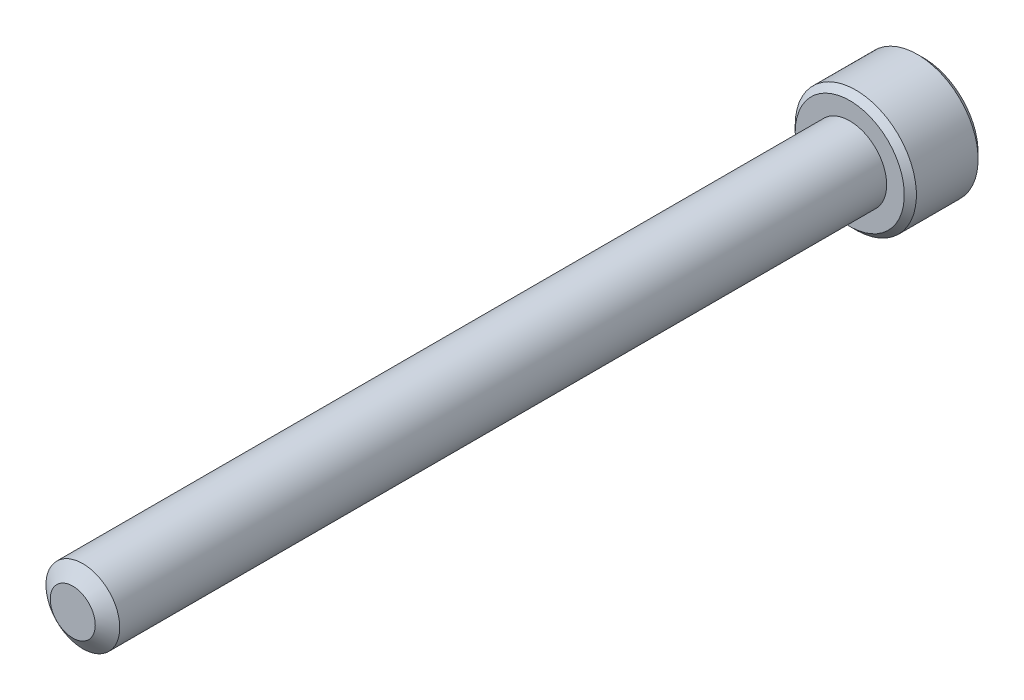
SolidWorks part; units mm, degrees
ref_plane "Front Plane" through (0, 0, 0) normal (0, 0, 1) x (1, 0, 0)
ref_plane "Top Plane" through (0, 0, 0) normal (0, 1, 0) x (1, 0, 0)
ref_plane "Right Plane" through (0, 0, 0) normal (1, 0, 0) x (0, 0, -1)
sketch "Sketch1" plane through (0, 0, 0) normal (0, 0, 1) x (1, 0, 0)
  circle A0 centre (0, 0) radius 2.413
  dimension "OD" = 4.826
extrude "Extrude1" add sketch "Sketch1" against normal blind 50.8
sketch "Sketch2" plane through (0, 0, 0) normal (0, 0, 1) x (1, 0, 0)
  circle A0 centre (0, 0) radius 2.413 construction
  circle A1 centre (0, 0) radius 2.413
curve "Helix/Spiral1" pitch 1.0583 height 51.8583 turns 49 parameters "pitch"=1.0583
sketch "Sketch3" plane through (0, 0, 0) normal (1, 0, 0) x (0, 0, -1)
  line L0 (-0.926, 2.413) -> (-0.5292, 1.7256)
  line L1 (-0.5292, 1.7256) -> (-0.3969, 1.7256)
  line L2 (-0.3969, 1.7256) -> (0, 2.413)
  line L3 (-0.926, 2.413) -> (0, 2.413)
  line L4 (-0.463, 2.413) -> (-0.463, 1.7256) construction
  line L5 (-0.7276, 2.0693) -> (-0.1984, 2.0693) construction
  line L6 (0, 2.413) -> (0, -2.413) construction
  dimension "D1" = 0.1323
  dimension "D2" = 0.5292
  dimension "D3" = 60
sweep "Cut-Sweep1" [suppressed] cut profiles "Sketch3" path "Helix/Spiral1"
sketch "Sketch4" plane through (0, 0, 0) normal (1, 0, 0) x (0, 0, -1)
  line L0 (0.6592, 2.413) -> (0, 1.4716)
  line L1 (0, 1.4716) -> (0, 2.413)
  line L2 (0.6592, 2.413) -> (0, 2.413)
  line L3 (-0.926, 2.413) -> (0, 2.413) construction
  line L4 (0, 0) -> (7.0209, 0) construction
  dimension "D1" = 55
  dimension "D2" = 0.254
revolve "Cut-Revolve1" cut sketch "Sketch4" angle 360 about L4
sketch "Sketch6" plane through (0, 0, -50.8) normal (0, 0, -1) x (-1, 0, 0)
  circle A0 centre (0, 0) radius 3.9624
  dimension "head dia" = 7.9248
extrude "Extrude2" add sketch "Sketch6" along normal blind 4.826
sketch "Sketch7" plane through (0, 0, -55.626) normal (0, 0, -1) x (-1, 0, 0)
  line L1 (0, 2.2914) -> (-1.9844, 1.1457)
  line L2 (-1.9844, 1.1457) -> (-1.9844, -1.1457)
  line L3 (-1.9844, -1.1457) -> (0, -2.2914)
  line L4 (0, -2.2914) -> (1.9844, -1.1457)
  line L5 (1.9844, -1.1457) -> (1.9844, 1.1457)
  line L6 (1.9844, 1.1457) -> (0, 2.2914)
  circle A0 centre (0, 0) radius 1.9844 construction
  dimension "hex dia" = 3.9688
extrude "Cut-Extrude1" cut sketch "Sketch7" against normal blind 2.9766
sketch "Sketch8" plane through (0, 0, -55.626) normal (0, 0, -1) x (-1, 0, 0)
  circle A0 centre (0, 0) radius 2.2914
extrude "Cut-Extrude2" cut sketch "Sketch8" against normal through all draft 45
chamfer "Chamfer1" distance 0.3962 angle 45 2 edges at (-3.9624, 0, -55.626) (-3.9624, 0, -50.8)
sketch "Sketch10" plane through (0, 0, -50.8) normal (0, 0, 1) x (1, 0, 0)
  circle A0 centre (0, 0) radius 2.413
extrude "Partial Thread" [suppressed] add sketch "Sketch10" along normal offset from surface (19.05 mm away) 2.54 up to face at (1.4716, 0, 0)
sketch "Sketch9" plane through (0, 0, 0) normal (1, 0, 0) x (0, 0, -1)
  line L0 (0, 2.413) -> (0, -2.413) construction
  line L1 (1.5875, 2.413) -> (1.5875, -2.413) construction
  dimension "D1" = 1.5875
equation "\"D3@Helix/Spiral1\" = \"screw length@Extrude1\"+\"pitch@Helix/Spiral1\""
equation "\"D1@Sketch3\" = \"pitch@Helix/Spiral1\"*.125"
equation "\"D2@Sketch3\" = \"pitch@Helix/Spiral1\"*.5"
equation "\"D1@Cut-Extrude1\" = \"hex dia@Sketch7\"*.75"
equation "\"D1@Chamfer1\" = \"head dia@Sketch6\"*.05"
equation "\"D1@Sketch9\" = \"pitch@Helix/Spiral1\"*1.5"
